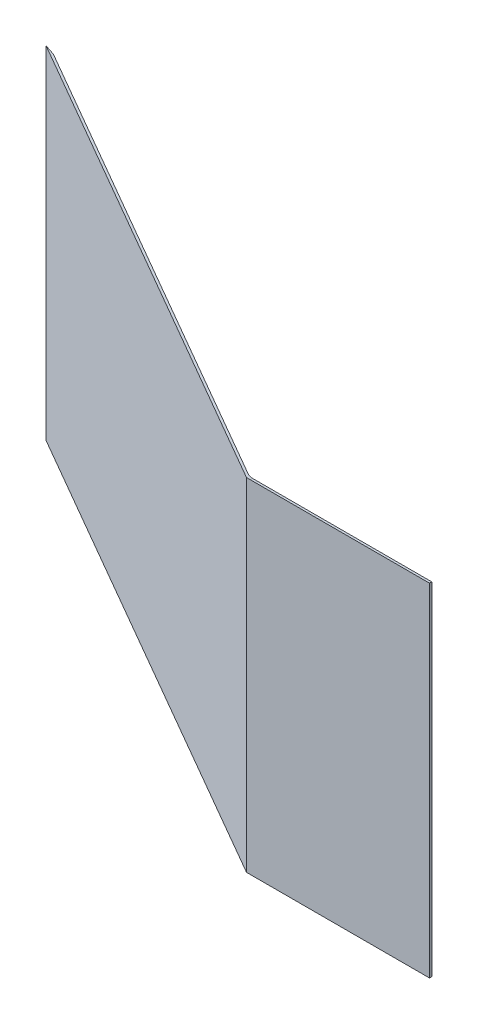
SolidWorks part; units mm, degrees
ref_plane "前视基准面" through (0, 0, 0) normal (0, 0, 1) x (1, 0, 0)
ref_plane "上视基准面" through (0, 0, 0) normal (0, 1, 0) x (1, 0, 0)
ref_plane "右视基准面" through (0, 0, 0) normal (1, 0, 0) x (0, 0, -1)
sketch "草图1" plane through (0, 0, 0) normal (0, 1, 0) x (1, 0, 0)
  line L0 (-84.9305, 76.3422) -> (118.5855, -41.1578)
  line L1 (118.5855, -41.1578) -> (198.5855, -41.1578)
  line L2 (-18.9202, 0) -> (18.7419, 0) construction
  line L3 (-89.5286, 77.8422) -> (118.3175, -42.1578)
  line L4 (118.3175, -42.1578) -> (198.5855, -42.1578)
  line L5 (-89.5286, 77.8422) -> (-84.9305, 76.3422)
  line L6 (198.5855, -41.1578) -> (198.5855, -42.1578)
  line L7 (-89.0286, 78.7083) -> (118.5855, -41.1578) construction
  dimension "D1" = 240
  dimension "D2" = 150
  dimension "D3" = 235
  dimension "D4" = 80
  dimension "D5" = 1
extrude "凸台-拉伸1" add sketch "草图1" along normal blind 10
extrude "凸台-拉伸2" add sketch "草图1<2>" along normal blind 150
sketch "草图1<2>" plane through (0, 0, 0) normal (0, 1, 0) x (1, 0, 0) same geometry as "草图1"
fillet "圆角1" radius 5 1 edges at (-84.9305, 75, -76.3422)
fillet "圆角2" radius 5 1 edges at (118.5855, 75, 41.1578)
